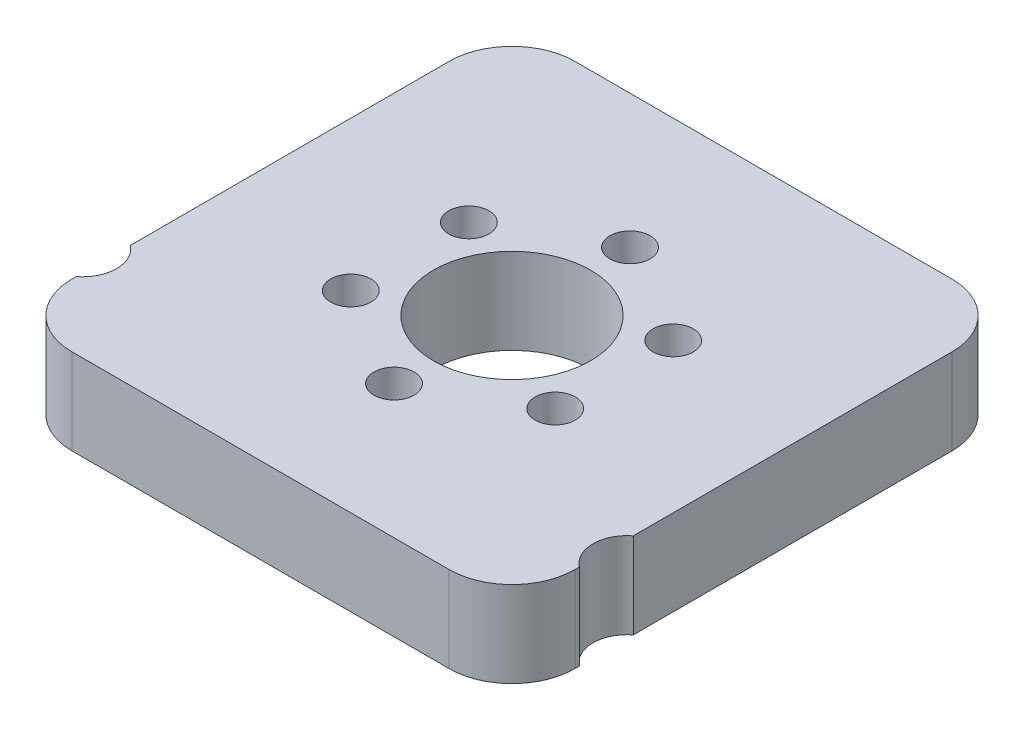
SolidWorks part; units mm, degrees
ref_plane "Front Plane" through (0, 0, 0) normal (0, 0, 1) x (1, 0, 0)
ref_plane "Top Plane" through (0, 0, 0) normal (0, 1, 0) x (1, 0, 0)
ref_plane "Right Plane" through (0, 0, 0) normal (1, 0, 0) x (0, 0, -1)
sketch "Sketch1" plane through (0, 0, 0) normal (0, 1, 0) x (1, 0, 0)
  line L0 (0, 0) -> (0, 35.4208) construction
  line L1 (-20, -20) -> (20, -20)
  line L2 (-20, -20) -> (-20, 20)
  line L3 (-20, 20) -> (20, 20)
  line L4 (20, -20) -> (20, 20)
  line L5 (-20, -20) -> (20, 20) construction
  line L6 (-20, 20) -> (20, -20) construction
  circle A0 centre (0, 0) radius 6.25
  circle A1 centre (0, 25) radius 2.7073
  circle A2 centre (21.6506, -12.5) radius 2.7073
  circle A3 centre (-21.6506, -12.5) radius 2.7073
  point P0 (0, 0)
  point P18 (0, 0)
  dimension "D2" = 12.5
  dimension "D1" = 25
  dimension "D3" = 40
  dimension "D4" = 40
  dimension "D5" = 3
extrude "Boss-Extrude1" add sketch "Sketch1" along normal blind 6.825 contours A3 L2 L1 L4 A2 L3 A0 region at (-19.4343, 0, 17.3229)
sketch "Sketch7" plane through (0, 6.825, 0) normal (0, 1, 0) x (1, 0, 0)
  circle A0 centre (0, 0) radius 22.5
  circle A1 centre (0, 0) radius 6.25
  dimension "D1" = 45
  dimension "D2" = 12.5
extrude "Boss-Extrude2" [suppressed] add sketch "Sketch7" along normal blind 5
sketch "Sketch5" [suppressed] plane through (0, 0, 0) normal (1, 0, 0) x (0, 0, -1)
  line L0 (-10.331, 15) -> (10.331, 0) construction
  line L1 (10, 5) -> (-10, 5)
  line L2 (10, 5) -> (10, 10)
  line L3 (10, 10) -> (-10, 10)
  line L4 (-10, 5) -> (-10, 10)
  line L5 (10, 5) -> (-10, 10) construction
  line L6 (10, 10) -> (-10, 5) construction
  line L7 (20, 7.5) -> (-20, 7.5) construction
  line L8 (20, 15) -> (20, 0) construction
  line L9 (-20, 15) -> (-20, 0) construction
  line L10 (-10.3541, 15) -> (-10.3078, 15) construction
  line L11 (-10.3541, 0) -> (20, 0) construction
  point P0 (0, 7.5)
  dimension "D1" = 20
  dimension "D2" = 5
extrude "Square side-insert" [suppressed] cut sketch "Sketch5" against normal up to surface (20 mm away)
sketch "Sketch3" [suppressed] plane through (0, 0, -20) normal (0, 0, -1) x (-1, 0, 0)
  line L3 (15.1539, 15) -> (15.1539, 3) construction
  line L4 (20, 15) -> (10.3078, 15) construction
  circle A0 centre (15.1539, 3) radius 1.6
  dimension "D2" = 3.2
  dimension "D1" = 12
extrude "Single Screw" [suppressed] cut sketch "Sketch3" against normal blind 17
sketch "Sketch2" [suppressed] plane through (0, 0, 20) normal (0, 0, 1) x (1, 0, 0)
  line L0 (0, 27.8717) -> (0, -11.9207) construction
  line L1 (20, 2) -> (10, 2)
  line L3 (10, 2) -> (10, 0)
  line L4 (-20, 0) -> (20, 0) construction
  line L5 (20, 15) -> (20, 0) construction
  circle A0 centre (10, 2) radius 1.6
  circle A1 centre (-10, 2) radius 1.6
  dimension "D3" = 3.2
  dimension "D1" = 10
  dimension "D2" = 2
extrude "Double Screw" [suppressed] cut sketch "Sketch2" against normal blind 10 contours A1 | A0
sketch "Sketch6" plane through (0, 6.825, 0) normal (0, 1, 0) x (1, 0, 0)
  circle A9 centre (0, -9.385) radius 1.6
  circle A10 centre (-8.1276, -4.6925) radius 1.6
  circle A11 centre (-8.1276, 4.6925) radius 1.6
  circle A12 centre (0, 9.385) radius 1.6
  circle A13 centre (8.1276, 4.6925) radius 1.6
  circle A14 centre (8.1276, -4.6925) radius 1.6
  point P16 (0, 0)
  dimension "D2" = 9.385
  dimension "D1" = 3.2
  dimension "D3" = 9.385
extrude "Cut-Extrude1" cut sketch "Sketch6" against normal through all
sketch "Sketch8" [suppressed] plane through (0, 12, 0) normal (0, 1, 0) x (1, 0, 0)
  line L0 (-20, 5) -> (-20, -5)
  line L1 (-20, -5) -> (-3.75, -5) construction
  line L2 (-20, 5) -> (-3.75, 5) construction
  line L3 (-20, -10.3541) -> (-20, -10.3078) construction
  line L4 (-20, 5) -> (-20, 12.5)
  line L6 (-20, -5) -> (-20, -12.5)
  line L8 (-20, 12.5) -> (-13.9645, 6.4645)
  line L9 (-10.4289, 5) -> (-3.75, 5)
  line L10 (-20, -12.5) -> (-13.9645, -6.4645)
  line L11 (-10.4289, -5) -> (-3.75, -5)
  circle A0 centre (0, 0) radius 6.25 construction
  arc A1 (-3.75, 5) -> (-3.75, -5) centre (0, 0) ccw
  arc A2 (-13.9645, -6.4645) -> (-10.4289, -5) centre (-10.4289, -10) cw
  arc A3 (-10.4289, 5) -> (-13.9645, 6.4645) centre (-10.4289, 10) cw
  point P6 (-20, 0)
  point P19 (-12.5, -5)
  point P22 (-12.5, 5)
  dimension "D2" = 7.5
  dimension "D5" = 5
  dimension "D1" = 10
  dimension "D3" = 7.5
  dimension "D4" = 7.5
extrude "Cut-Extrude3" [suppressed] cut sketch "Sketch8" against normal blind 5 from offset 5 offset against normal yes
fillet "Fillet2" radius 5 4 edges at (20, 3.4125, 20) (20, 3.4125, -20) (-20, 3.4125, -20) (-20, 3.4125, 20)
fillet "Fillet3" [suppressed] radius 3
